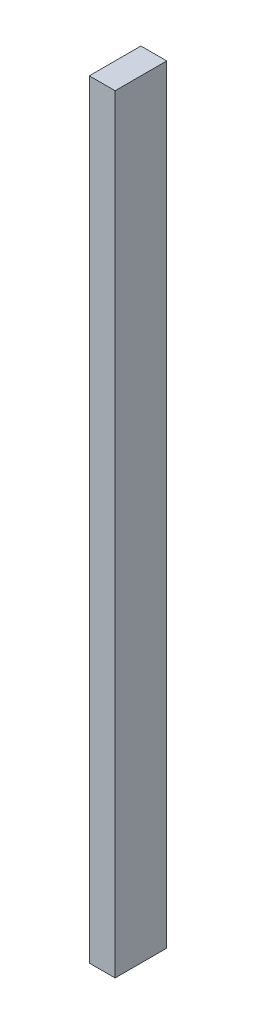
SolidWorks part; units mm, degrees
note: The reader was unsure of these and kept them because the rebuilt part matched: shared geometry of "Sketch1<5>".
ref_plane "Front Plane" through (0, 0, 0) normal (1, 0, 0) x (0, 1, 0)
ref_plane "Top Plane" through (0, 0, 0) normal (0, 0, 1) x (0, 1, 0)
ref_plane "Right Plane" through (0, 0, 0) normal (0, 1, 0) x (-1, 0, 0)
sketch "Sketch1" plane through (0, 0, 0) normal (0, 0, 1) x (0, 1, 0)
  line L0 (2.5, 8) -> (2.5, 0)
  line L1 (0, 0) -> (238, 0)
  line L2 (0, 0) -> (0, 8)
  line L3 (0, 8) -> (238, 8)
  line L4 (238, 0) -> (238, 8)
  circle A0 centre (2.5, 4) radius 0.795
  dimension "D3" = 1.59
  dimension "D1" = 238
  dimension "D2" = 8
  dimension "D4" = 4
  dimension "D5" = 2.5
extrude "Boss-Extrude1" add sketch "Sketch1" along normal blind 16 contours A0 | L1 L4 L3 L2 A0 | A0 L0 L3 L2 L1 | L0 A0
revolve "Cut-Revolve1" cut sketch "Sketch1<5>" angle 360 about L0
sketch "Sketch1<5>" plane through (0, 0, 0) normal (0, 0, 1) x (0, 1, 0) same geometry as "Sketch1"
pattern_linear "LPattern1" count 2 spacing 2.5 along (0, 1, 0) of "Cut-Revolve1"
pattern_linear "LPattern3" count 39 spacing 6 along (0, 1, 0) of "LPattern1", "Cut-Revolve1"
